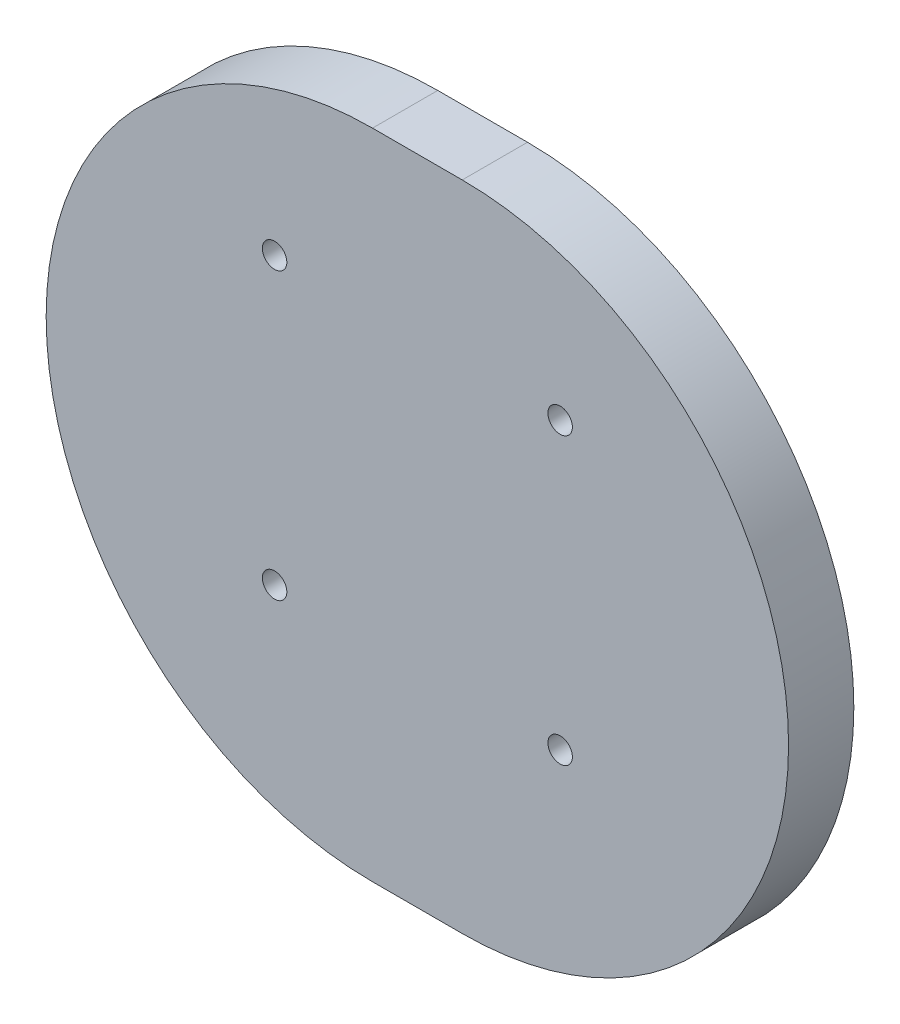
SolidWorks part; units mm, degrees
ref_plane "Front Plane" through (0, 0, 0) normal (0, 0, 1) x (1, 0, 0)
ref_plane "Top Plane" through (0, 0, 0) normal (0, 1, 0) x (1, 0, 0)
ref_plane "Right Plane" through (0, 0, 0) normal (1, 0, 0) x (0, 0, -1)
sketch "Sketch1" plane through (0, 0, 0) normal (0, 0, 1) x (1, 0, 0)
  line L0 (-1.1, 0) -> (1.1, 0) construction
  line L1 (-1.1, 8) -> (1.1, 8)
  line L2 (-1.1, -8) -> (1.1, -8)
  line L4 (3.5, -2.9) -> (-3.5, -2.9) construction
  line L5 (3.5, -2.9) -> (3.5, 4.1) construction
  line L6 (3.5, 4.1) -> (-3.5, 4.1) construction
  line L7 (-3.5, -2.9) -> (-3.5, 4.1) construction
  arc A0 (-1.1, 8) -> (-1.1, -8) centre (-1.1, 0) ccw
  arc A1 (1.1, -8) -> (1.1, 8) centre (1.1, 0) ccw
  circle A2 centre (3.5, 4.1) radius 0.3
  circle A3 centre (-3.5, 4.1) radius 0.3
  circle A4 centre (-3.5, -2.9) radius 0.3
  circle A5 centre (3.5, -2.9) radius 0.3
  point P3 (0, 0)
  point P12 (3.5, 0.6)
  point P13 (0, 4.1)
  point P14 (0, 8)
  dimension "D1" = 8
  dimension "D6" = 0.6
  dimension "D7" = 0.6
  dimension "D8" = 0.6
  dimension "D9" = 0.6
  dimension "D2" = 2.2
  dimension "D3" = 7.4
  dimension "D4" = 7
  dimension "D5" = 7
extrude "Boss-Extrude1" add sketch "Sketch1" along normal blind 1.6
